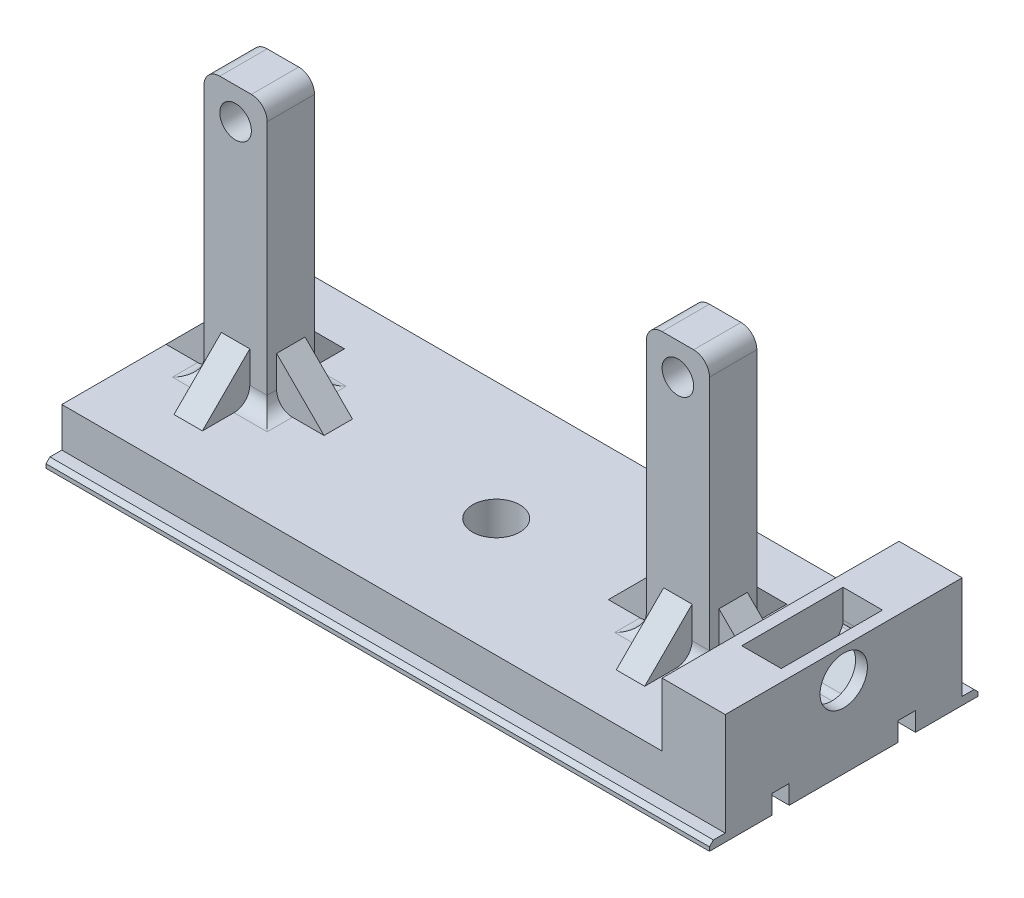
SolidWorks part; units mm, degrees
ref_plane "Alzado" through (0, 0, 0) normal (0, 0, 1) x (1, 0, 0)
ref_plane "Planta" through (0, 0, 0) normal (0, 1, 0) x (1, 0, 0)
ref_plane "Vista lateral" through (0, 0, 0) normal (1, 0, 0) x (0, 0, -1)
sketch "Croquis1" plane through (0, 0, 0) normal (0, 0, 1) x (1, 0, 0)
  line L0 (0, 0) -> (38, 0)
  line L1 (38, 0) -> (38, 3)
  line L2 (38, 3) -> (35, 3)
  line L3 (35, 3) -> (35, 20)
  line L4 (35, 20) -> (31, 20)
  line L5 (31, 20) -> (31, 3)
  line L6 (31, 3) -> (7, 3)
  line L7 (7, 3) -> (7, 20)
  line L8 (7, 20) -> (3, 20)
  line L9 (3, 20) -> (3, 3)
  line L10 (0, 0) -> (0, 3)
  line L11 (0, 3) -> (3, 3)
  circle A0 centre (5, 18) radius 1
  circle A1 centre (33, 18) radius 1
  point P19 (5, 20)
  point P21 (33, 20)
  dimension "D1" = 2
  dimension "D2" = 28
  dimension "D3" = 15
  dimension "D4" = 2
  dimension "D5" = 3
  dimension "D6" = 4
  dimension "D7" = 3
extrude "Saliente-Extruir1" add sketch "Croquis1" along normal mid plane 3
sketch "Croquis2" plane through (0, 0, 1.5) normal (0, 0, 1) x (1, 0, 0)
  line L1 (0, 3) -> (38, 3)
  line L2 (0, 3) -> (0, 0)
  line L3 (0, 0) -> (38, 0)
  line L4 (38, 3) -> (38, 0)
extrude "Saliente-Extruir2" add sketch "Croquis2" along normal blind 6
sketch "Croquis3" plane through (0, 0, -1.5) normal (0, 0, -1) x (-1, 0, 0)
  line L1 (-38, 3) -> (0, 3)
  line L2 (-38, 3) -> (-38, 0)
  line L3 (-38, 0) -> (0, 0)
  line L4 (0, 3) -> (0, 0)
extrude "Saliente-Extruir3" add sketch "Croquis3" along normal blind 6
fillet "Redondeo1" radius 1 4 edges at (35, 20, 0) (31, 20, 0) (7, 20, 0) (3, 20, 0)
sketch "Croquis4" plane through (0, 0, 0) normal (0, 0, 1) x (1, 0, 0)
  line L3 (35, 6) -> (38, 3)
  line L4 (35, 3) -> (35, 19) construction
  dimension "D2" = 3
  dimension "D4" = 3
rib "Nervio1" sketch "Croquis4" sketch "Croquis4" thickness 1.8 extrusion direction parallel to sketch draft on no parameters "D1"=1.8
sketch "Croquis5" plane through (0, 0, 0) normal (0, 0, 1) x (1, 0, 0)
  line L0 (31, 6) -> (28, 3)
  line L1 (31, 19) -> (31, 3) construction
  line L2 (38, 3) -> (0, 3) construction
  dimension "D1" = 3
  dimension "D2" = 3
rib "Nervio5" sketch "Croquis5" sketch "Croquis5" thickness 1.8 extrusion direction parallel to sketch draft on no parameters "D1"=1.8
ref_plane "Plano2" through (33, 0, 0) normal (1, 0, 0) x (0, 0, -1)
sketch "Croquis6" plane through (33, 0, 0) normal (1, 0, 0) x (0, 0, -1)
  line L0 (1.5, 6) -> (4.5, 3)
  line L1 (1.5, 3) -> (1.5, 19) construction
  line L2 (0.9, 3) -> (7.5, 3) construction
  dimension "D1" = 3
  dimension "D2" = 3
rib "Nervio6" sketch "Croquis6" sketch "Croquis6" thickness 1.8 extrusion direction parallel to sketch draft on no parameters "D1"=1.8
sketch "Croquis7" plane through (33, 0, 0) normal (1, 0, 0) x (0, 0, -1)
  line L0 (-1.5, 6) -> (-4.5, 3)
  line L1 (-1.5, 3) -> (-1.5, 19) construction
  line L2 (-7.5, 3) -> (-0.9, 3) construction
  dimension "D1" = 3
  dimension "D2" = 3
rib "Nervio7" sketch "Croquis7" sketch "Croquis7" thickness 1.8 extrusion direction parallel to sketch draft on no parameters "D1"=1.8
ref_plane "Plano1" through (19, 0, 0) normal (-1, 0, 0) x (0, 0, 1)
mirror "Simetría3" about plane through (19, 0, 0) normal (-1, 0, 0) of "Nervio1", "Nervio7", "Nervio6", "Nervio5"
fillet "Redondeo2" radius 1 16 edges at (31.55, 3, 1.5) (31, 3, 1.2) (34.45, 3, 1.5) (35, 3, 1.2) (35, 3, -1.2) (34.45, 3, -1.5) (31, 3, -1.2) (31.55, 3, -1.5) (3, 3, -1.2) (3.55, 3, -1.5) (6.45, 3, -1.5) (7, 3, -1.2) (7, 3, 1.2) (6.45, 3, 1.5) (3, 3, 1.2) (3.55, 3, 1.5)
sketch "Croquis8" plane through (0, 0, 0) normal (0, -1, 0) x (1, 0, 0)
  line L0 (0, 7.5) -> (0, -7.5) construction
  line L1 (0, 4.55) -> (38, 4.55)
  line L2 (0, 4.55) -> (0, 3.45)
  line L3 (0, 3.45) -> (38, 3.45)
  line L4 (38, 4.55) -> (38, 3.45)
  line L5 (38, 7.5) -> (38, -7.5) construction
  line L6 (0, 7.5) -> (38, 7.5) construction
  line L7 (0, -3.45) -> (38.2491, -3.45)
  line L8 (0, -3.45) -> (0, -4.55)
  line L9 (0, -4.55) -> (38.2491, -4.55)
  line L10 (38.2491, -3.45) -> (38.2491, -4.55)
  line L11 (38, -7.5) -> (0, -7.5) construction
  dimension "D1" = 2.95
  dimension "D2" = 2.95
  dimension "D3" = 1.1
  dimension "D4" = 1.1
extrude "Cortar-Extruir1" cut sketch "Croquis8" against normal blind 1.2
sketch "Croquis10" plane through (0, 3, 0) normal (0, 1, 0) x (1, 0, 0)
  line L1 (42, 7.5) -> (38, 7.5)
  line L2 (42, 7.5) -> (42, -7.5)
  line L3 (42, -7.5) -> (38, -7.5)
  line L4 (38, 7.5) -> (38, -7.5)
  line L6 (38, -7.5) -> (0, -7.5) construction
  line L7 (0, 7.5) -> (38, 7.5) construction
  dimension "D1" = 4
extrude "Saliente-Extruir5" add sketch "Croquis10" against normal up to surface (3 mm away) and the other way blind 4 from surface up to face at (19, 0, 0) starting at face at (19, 3, 0)
sketch "Croquis11" plane through (38, 0, 0) normal (-1, 0, 0) x (0, 0, 1)
  line L0 (7.5, 0) -> (-7.5, 0) construction
  line L1 (1.6454, 2.27) -> (3.2909, 5.12)
  line L2 (3.2909, 5.12) -> (1.6454, 7.97)
  line L3 (1.6454, 7.97) -> (-1.6454, 7.97)
  line L4 (-1.6454, 7.97) -> (-3.2909, 5.12)
  line L5 (-3.2909, 5.12) -> (-1.6454, 2.27)
  line L6 (-1.6454, 2.27) -> (1.6454, 2.27)
  circle A0 centre (0, 5.12) radius 2.85 construction
  circle A1 centre (0, 5.12) radius 1.5
  dimension "D1" = 5.7
  dimension "D3" = 3
  dimension "D2" = 5.12
extrude "Cortar-Extruir2" cut sketch "Croquis11" along normal mid plane 2.5 from offset 2 contours L4 L5 L6 L1 L2 L3 offset against normal yes
fillet "Redondeo5" radius 0.5 4 edges at (40, 5.12, -3.2909) (40, 2.27, -1.6454) (40, 5.12, 3.2909) (40, 2.27, 1.6454)
sketch "Croquis13" plane through (0, 0, 0) normal (0, -1, 0) x (1, 0, 0)
  line L0 (42, 7.5) -> (42, -7.5) construction
  line L1 (38, 4.55) -> (42, 4.55)
  line L2 (38, 4.55) -> (38, 3.45)
  line L3 (38, 3.45) -> (42, 3.45)
  line L4 (42, 4.55) -> (42, 3.45)
  line L5 (0, 3.45) -> (38, 3.45) construction
  line L6 (38, -3.45) -> (42, -3.45)
  line L7 (38, -3.45) -> (38, -4.55)
  line L8 (38, -4.55) -> (42, -4.55)
  line L9 (42, -3.45) -> (42, -4.55)
  line L10 (0, -4.55) -> (38, -4.55) construction
extrude "Cortar-Extruir4" cut sketch "Croquis13" against normal blind 1.2
sketch "Croquis14" plane through (0, 7, 0) normal (0, 1, 0) x (1, 0, 0)
  line L0 (38.75, 1.3568) -> (38.75, -1.3568) construction
  line L1 (38.75, 3.2055) -> (41.25, 3.2055)
  line L2 (38.75, 3.2055) -> (38.75, -3.2055)
  line L3 (38.75, -3.2055) -> (41.25, -3.2055)
  line L4 (41.25, 3.2055) -> (41.25, -3.2055)
  line L5 (41.25, 1.3568) -> (41.25, -1.3568) construction
  line L6 (41.25, -2.2055) -> (38.75, -2.2055) construction
  line L7 (38.75, 2.2055) -> (41.25, 2.2055) construction
  dimension "D1" = 1
  dimension "D2" = 1
extrude "Cortar-Extruir5" cut sketch "Croquis14" against normal blind 2
extrude "Cortar-Extruir6" cut sketch "Croquis11<3>" against normal blind 4 from surface contours A1 starting at face at (41.25, 4.605, 0)
sketch "Croquis11<3>" plane through (38, 0, 0) normal (-1, 0, 0) x (0, 0, 1) same geometry as "Croquis11"
sketch "Croquis15" plane through (0, 0, 0) normal (-1, 0, 0) x (0, 0, 1)
  line L0 (-7.5, 0) -> (-8.5, 0)
  line L1 (-8.5, 0) -> (-8.5, 0.5)
  line L2 (-8.5, 0.5) -> (-7.5, 0.5)
  line L3 (-7.5, 0) -> (-7.5, 3) construction
  line L4 (7.5, 0.5) -> (8.5, 0.5)
  line L5 (7.5, 3) -> (7.5, 0) construction
  line L6 (8.5, 0.5) -> (8.5, 0)
  line L7 (8.5, 0) -> (7.5, 0)
  line L8 (7.5, 0) -> (4.55, 0) construction
  line L9 (7.5, 0) -> (7.5, 0.5)
  line L10 (-7.5, 0.5) -> (-7.5, 0)
  dimension "D1" = 1
  dimension "D2" = 1
  dimension "D3" = 0.5
extrude "Saliente-Extruir6" add sketch "Croquis15" against normal up to surface (42 mm away) up to face at (42, 5.12, 1.5)
chamfer "Chaflán1" distance 0.25 angle 45 2 edges at (21, 0.5, 8.5) (21, 0.5, -8.5)
sketch "Croquis16" plane through (0, 3, 0) normal (0, 1, 0) x (1, 0, 0)
  line L0 (0, 0.9) -> (0, 7.5) construction
  circle A0 centre (20, 0) radius 1.5
  point P5 (0, 0)
  dimension "D1" = 3
  dimension "D2" = 20
extrude "Cortar-Extruir7" cut sketch "Croquis16" against normal up to next
equation "\"h\"= 15"
equation "\"D3@Croquis1\"=\"h\""
